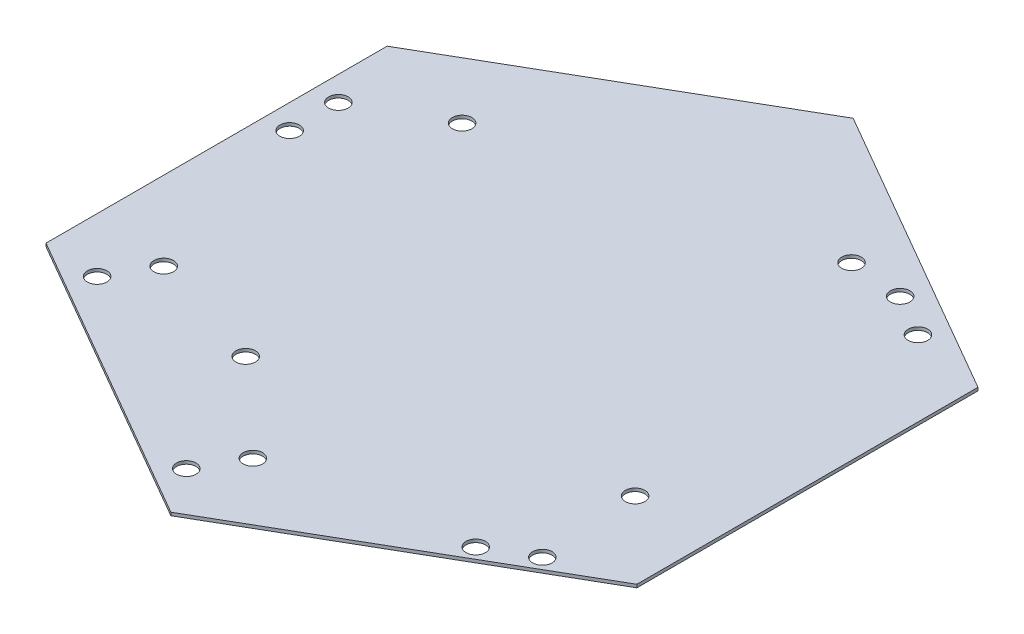
SolidWorks part; units mm, degrees
material "5052-H32"
ref_plane "Front Plane" through (0, 0, 0) normal (0, 0, 1) x (1, 0, 0)
ref_plane "Top Plane" through (0, 0, 0) normal (0, 1, 0) x (1, 0, 0)
ref_plane "Right Plane" through (0, 0, 0) normal (1, 0, 0) x (0, 0, -1)
sketch "Sketch1" plane through (0, 0, 0) normal (0, 1, 0) x (1, 0, 0)
  line L0 (47.5884, -57.0254) -> (58.5869, -50.6754) construction
  line L1 (0, 88.9) -> (-76.9897, 44.45)
  line L2 (-76.9897, 44.45) -> (-76.9897, -44.45)
  line L3 (-76.9897, -44.45) -> (0, -88.9)
  line L4 (0, -88.9) -> (76.9897, -44.45)
  line L5 (76.9897, -44.45) -> (76.9897, 44.45)
  line L6 (76.9897, 44.45) -> (0, 88.9)
  line L7 (58.5869, -50.6754) -> (60.4919, -53.975) construction
  line L8 (-70.6397, 12.7) -> (-76.9897, 12.7) construction
  line L9 (-70.6397, 25.4) -> (-70.6397, 12.7) construction
  line L10 (46.3184, 54.8257) -> (49.4934, 60.325) construction
  line L11 (57.3169, 48.4757) -> (46.3184, 54.8257) construction
  line L12 (47.5884, -57.0254) -> (49.4934, -60.325) construction
  circle A0 centre (0, 0) radius 76.9897 construction
  circle A1 centre (47.5884, -57.0254) radius 2.54
  circle A2 centre (58.5869, -50.6754) radius 2.54
  circle A7 centre (-70.6397, 12.7) radius 2.54
  circle A8 centre (-70.6397, 25.4) radius 2.54
  circle A9 centre (46.3184, 54.8257) radius 2.54
  circle A10 centre (57.3169, 48.4757) radius 2.54
  point P13 (38.4948, -66.675)
  point P28 (3.175, -1.8331)
  point P29 (0, 0)
  dimension "D2" = 5.08
  dimension "D3" = 3.81
  dimension "D4" = 12.7
  dimension "D1" = 177.8
  dimension "D5" = 12.7
extrude "Boss-Extrude1" add sketch "Sketch1" along normal blind 0.8128
sketch "Sketch2" plane through (0, 0.8128, 0) normal (0, 1, 0) x (1, 0, 0)
  line L0 (-49.8503, 36.8467) -> (56.8353, -24.7483) construction
  line L1 (27.9428, -74.7916) -> (-78.7428, -13.1966) construction
  line L2 (27.9428, -74.7916) -> (85.7278, 25.295) construction
  line L3 (85.7278, 25.295) -> (-20.9578, 86.89) construction
  line L4 (-78.7428, -13.1966) -> (-20.9578, 86.89) construction
  line L5 (-76.9897, -44.45) -> (0, -88.9) construction
  line L6 (32.385, 56.0925) -> (-25.4, -43.9941) construction
  circle A0 centre (-49.8503, 36.8467) radius 2.54
  circle A1 centre (-25.4, -43.9941) radius 2.54
  circle A2 centre (32.385, 56.0925) radius 2.54
  circle A3 centre (56.8353, -24.7483) radius 2.54
  dimension "D5" = 5.08
  dimension "D6" = 57.785
  dimension "D1" = 123.19
  dimension "D2" = 115.57
  dimension "D3" = 61.595
  dimension "D4" = 50.8
  dimension "D7" = 61.595
extrude "Cut-Extrude1" cut sketch "Sketch2" against normal through all
sketch "Sketch3" plane through (0, 0.8128, 0) normal (0, 1, 0) x (1, 0, 0)
  line L0 (-62.8161, -45.3007) -> (-65.9911, -50.8) construction
  line L2 (-76.9897, -44.45) -> (0, -88.9) construction
  line L3 (-62.8161, -45.3007) -> (-7.8235, -77.0507) construction
  line L4 (-35.3198, -61.1757) -> (-38.4948, -66.675) construction
  line L5 (-56.4661, -34.3022) -> (-62.8161, -45.3007) construction
  line L6 (-56.4661, -34.3022) -> (-1.4735, -66.0522) construction
  circle A1 centre (-7.8235, -77.0507) radius 2.54
  circle A2 centre (-62.8161, -45.3007) radius 2.54
  circle A3 centre (-56.4661, -34.3022) radius 2.54
  circle A4 centre (-1.4735, -66.0522) radius 2.54
  dimension "D1" = 5.08
  dimension "D2" = 6.35
  dimension "D3" = 63.5
  dimension "D4" = 12.7
extrude "Cut-Extrude2" cut sketch "Sketch3" against normal through all
